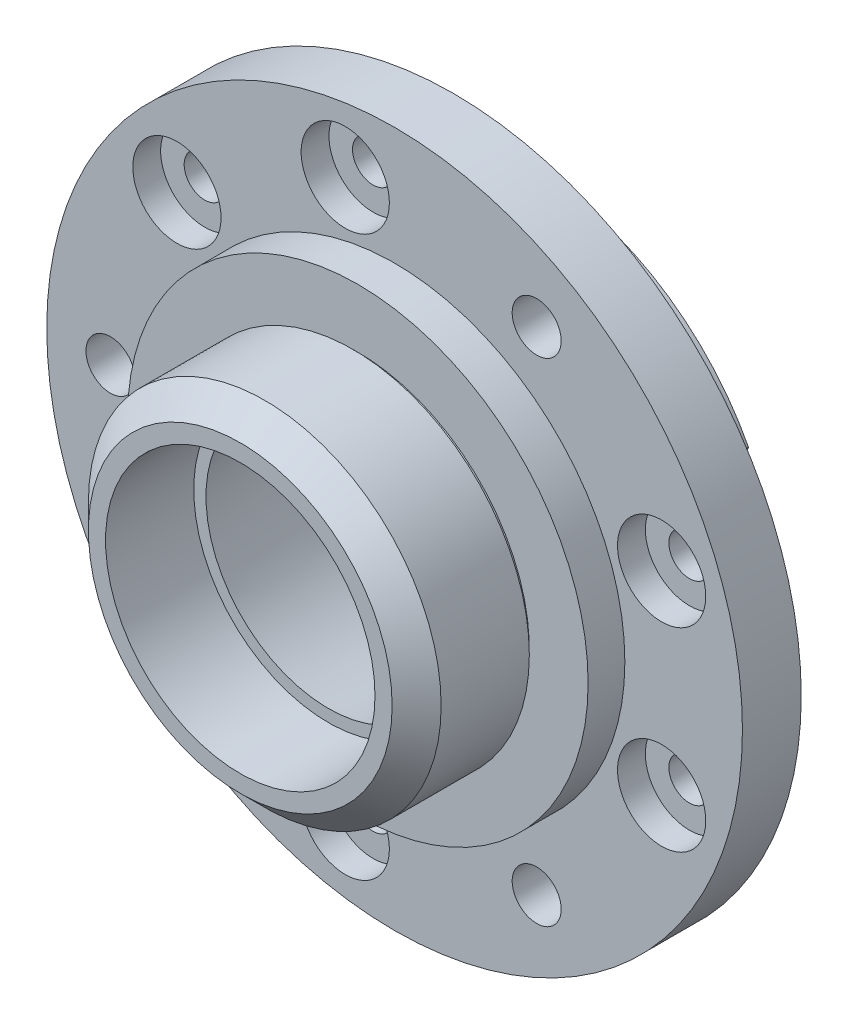
SolidWorks part; units mm, degrees
material "AISI 4340 Steel, annealed"
ref_plane "Front Plane" through (0, 0, 0) normal (0, 0, 1) x (1, 0, 0)
ref_plane "Top Plane" through (0, 0, 0) normal (0, 1, 0) x (1, 0, 0)
ref_plane "Right Plane" through (0, 0, 0) normal (1, 0, 0) x (0, 0, -1)
sketch "Sketch2" plane through (0, 0, 0) normal (0, 1, 0) x (1, 0, 0)
  line L0 (-76.4125, 0) -> (-63, 0)
  line L1 (-53, 0) -> (-49, 0)
  line L2 (49, 0) -> (76.4125, 0)
  line L3 (49, 0) -> (71, 0)
  line L4 (49, 0) -> (47, 0)
  line L5 (47, 0) -> (47, -2)
  line L6 (31, 25) -> (31, 9)
  line L7 (-31, 4) -> (-31, 20)
  line L8 (28, 9) -> (25, -13.5)
  line L9 (31, 25) -> (31, 9)
  line L10 (27.5, -13.5) -> (27.5, -26.5)
  line L11 (-27.5, -16.5) -> (-27.5, -3.5)
  line L12 (47, -9.5) -> (47, -31.5)
  line L13 (27.5, -13.5) -> (27.5, -26.5)
  line L14 (31, 9) -> (28, 9)
  line L15 (-28, 4) -> (-31, 4)
  line L17 (31, 9) -> (28, 9)
  line L18 (-27.5, -3.5) -> (-25, -3.5)
  line L19 (25, -13.5) -> (27.5, -13.5)
  line L20 (25, -13.5) -> (27.5, -13.5)
  line L22 (47, -2) -> (47, -9.5)
  line L23 (-47, -9.5) -> (-47, -2)
  line L24 (27.5, -26.5) -> (27.5, -31.5)
  line L25 (47, -2) -> (47, -9.5)
  line L26 (27.5, -31.5) -> (47, -31.5)
  line L27 (71, 0) -> (71, 12)
  line L28 (31, 25) -> (31, 27)
  line L29 (31, 27) -> (51, 27)
  line L30 (71, 12) -> (51, 12)
  line L31 (51, 12) -> (51, 27)
  line L32 (0, -21.1105) -> (0, 68.8895) construction
  line L33 (0, -21.1105) -> (0, 68.8895) construction
  dimension "D1" = 2
  dimension "D2" = 40
  dimension "D3" = 5
  dimension "D4" = 12
  dimension "D5" = 20
revolve "Revolve1" add sketch "Sketch2" angle 360 about L33
sketch "Sketch4" plane through (0, 0, 0) normal (0, 0, 1) x (1, 0, 0)
  circle A3 centre (0, 0) radius 58
  circle A4 centre (0, 0) radius 58 construction
  circle A5 centre (29, -50.2295) radius 5
  circle A6 centre (29, -50.2295) radius 5
  circle A7 centre (29, 50.2295) radius 5
  circle A8 centre (29, 50.2295) radius 5
  circle A9 centre (-58, 0) radius 5
  circle A10 centre (-58, 0) radius 5
  dimension "D1" = 0
  dimension "D2" = 0
  dimension "D3" = 0
  dimension "D4" = 0
extrude "Cut-Extrude1" cut sketch "Sketch4" against normal through all
hole_wizard "CBORE for M8 Hex Head Bolt1" positions "Sketch5" profile "Sketch6" counterbore size "M8" standard "ANSI Metric"
sketch "Sketch5" plane through (0, 0, 0) normal (0, 0, 1) x (1, 0, 0)
  line L0 (-44.4306, 37.2817) -> (0, 0) construction
  line L1 (0, 0) -> (-10.0716, 57.1188) construction
  line L4 (0, 0) -> (54.5022, 19.8372) construction
  line L7 (0, 0) -> (54.5022, -19.8372) construction
  line L10 (-44.4306, -37.2817) -> (0, 0) construction
  line L11 (0, 0) -> (-10.0716, -57.1188) construction
  line L14 (-58, 0) -> (0, 0) construction
  line L15 (0, 0) -> (29, 50.2295) construction
  line L18 (0, 0) -> (29, -50.2295) construction
  line L21 (-29, 0) -> (-22.2153, -18.6408) construction
  line L22 (-22.2153, -18.6408) -> (-5.0358, -28.5594) construction
  line L23 (-5.0358, -28.5594) -> (14.5, -25.1147) construction
  line L24 (14.5, -25.1147) -> (27.2511, -9.9186) construction
  line L25 (27.2511, -9.9186) -> (27.2511, 9.9186) construction
  line L26 (27.2511, 9.9186) -> (14.5, 25.1147) construction
  line L27 (14.5, 25.1147) -> (-5.0358, 28.5594) construction
  line L28 (-5.0358, 28.5594) -> (-22.2153, 18.6408) construction
  line L29 (-22.2153, 18.6408) -> (-29, 0) construction
  circle A0 centre (0, 0) radius 58 construction
  point P0 (-10.0716, 57.1188)
  point P4 (-44.4306, 37.2817)
  point P6 (-44.4306, -37.2817)
  point P8 (-10.0716, -57.1188)
  point P10 (54.5022, -19.8372)
  point P12 (54.5022, 19.8372)
sketch "Sketch6" plane through (-10.0716, 57.1188, 0) normal (1, 0, 0) x (0, -1, 0)
  line L0 (0, 0) -> (0, 30.9336)
  line L1 (0, 30.9336) -> (4.2, 28.41)
  line L2 (4.2, 28.41) -> (4.2, 5.68)
  line L3 (4.2, 5.68) -> (9.005, 5.68)
  line L4 (9.005, 5.68) -> (9.005, 0)
  line L5 (9.005, 0) -> (0, 0)
  line L10 (0, 30.9336) -> (-4.2, 28.41) construction
  line L11 (0, -6.35) -> (0, 107.95) construction
  dimension "Hole Dia." = 8.4
  dimension "Hole Depth" = 28.41
  dimension "C'Bore Dia." = 18.01
  dimension "C'Bore Depth" = 5.68
  dimension "Drill Angle" = 118
sketch "Sketch7" plane through (0, 0, 0) normal (0, 1, 0) x (1, 0, 0)
  line L0 (67.825, -9.5) -> (47, -9.5)
  line L1 (-47, -9.5) -> (-53, -9.5)
  line L2 (-63, -9.5) -> (-67.825, -9.5)
  line L3 (47, -9.5) -> (47, -7.5)
  line L4 (47, -31.5) -> (47, 0) construction
  line L5 (67.825, -9.5) -> (47, -9.5)
  line L6 (47, -7.5) -> (35, -7.5)
  line L7 (36, -8.5) -> (36, -31.5)
  line L8 (36, -31.5) -> (67.825, -31.5)
  line L9 (67.825, -31.5) -> (67.825, -9.5)
  line L10 (-27.5, -31.5) -> (-27.5, -13.5)
  line L11 (27.5, -13.5) -> (27.5, -31.5)
  line L12 (27.5, -13.5) -> (27.5, -31.5) construction
  line L13 (-47, -31.5) -> (47, -31.5) construction
  line L14 (36, -8.5) -> (35, -8.5)
  line L15 (35, -8.5) -> (35, -7.5)
  line L16 (-27.5, -13.5) -> (-27.5, -31.5) construction
  line L17 (-27.5, -13.5) -> (-27.5, -31.5) construction
  line L18 (-27.5, -22.5) -> (27.5, -22.5) construction
  line L19 (0, -7.5) -> (0, -37.5) construction
  point P28 (0, -22.5)
  dimension "D1" = 8.5
  dimension "D2" = 2
  dimension "D3" = 1
  dimension "D4" = 1
  dimension "D5" = 30
revolve "Cut-Revolve1" cut sketch "Sketch7" angle 360 about L19
chamfer "Chamfer1" distance 5 angle 45 1 edges at (-36, 0, 31.5)
sketch "Sketch8" plane through (0, 0, -27) normal (0, 0, -1) x (-1, 0, 0)
  circle A0 centre (44.4306, 37.2817) radius 10
  dimension "D1" = 20
extrude "Cut-Extrude2" cut sketch "Sketch8" against normal up to surface (15 mm away) up to face at (-14.2716, 57.1188, -12)
pattern_circular "CirPattern1" count 9 over 360 about axis through (0, 0, -12) along (0, 0, 1) skipping 1, 4, 7 of "Cut-Extrude2"
